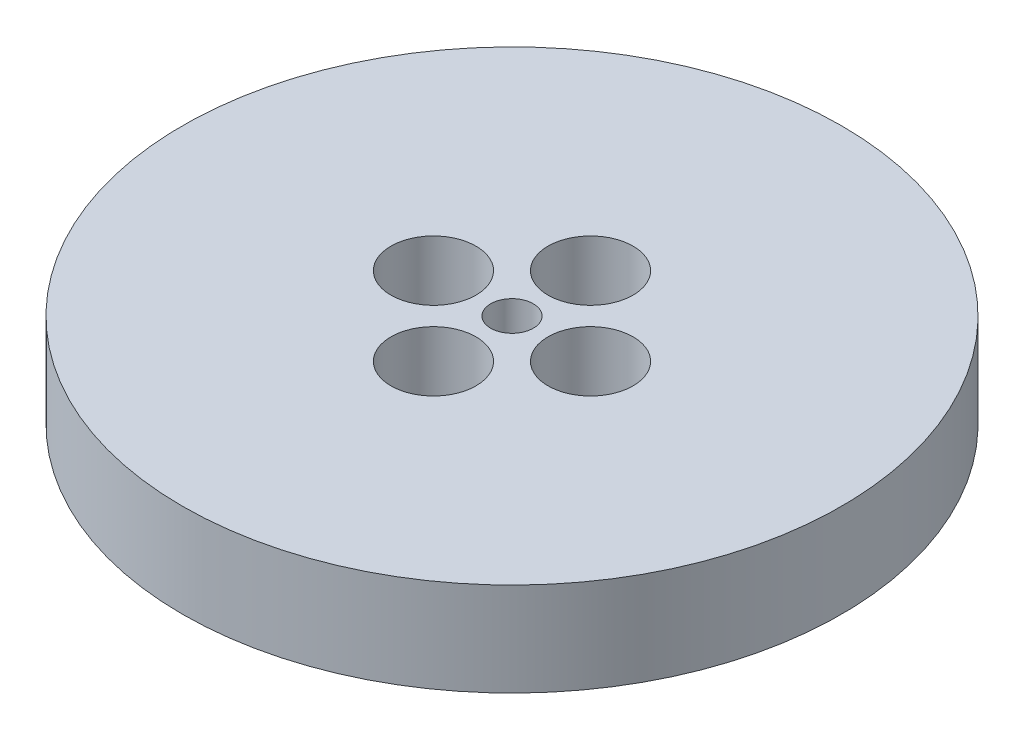
SolidWorks part; units mm, degrees
ref_plane "Front Plane" through (0, 0, 0) normal (0, 0, 1) x (1, 0, 0)
ref_plane "Top Plane" through (0, 0, 0) normal (0, 1, 0) x (1, 0, 0)
ref_plane "Right Plane" through (0, 0, 0) normal (1, 0, 0) x (0, 0, -1)
sketch "Sketch1" plane through (0, 0, 0) normal (0, 1, 0) x (1, 0, 0)
  circle A0 centre (0, 0) radius 77.5
  dimension "FLANGE_OD" = 155
extrude "Boss-Extrude1" add sketch "Sketch1" along normal blind 22
sketch "Sketch2" plane through (0, 0, 0) normal (0, 1, 0) x (1, 0, 0)
  circle A0 centre (0, 0) radius 5
  dimension "BORE_D" = 10
extrude "Cut-Extrude1" cut sketch "Sketch2" along normal through all
sketch "Sketch3" plane through (0, 22, 0) normal (0, 1, 0) x (1, 0, 0)
  circle A0 centre (0, 0) radius 18.4702 construction
  circle A1 centre (-18.4702, 0) radius 10
  dimension "BOLT_D" = 20
  dimension "BOLT_PCD" = 36.9403
extrude "Cut-Extrude2" cut sketch "Sketch3" against normal blind 16.5711
pattern_circular "CirPattern1" count 4 over 360 about axis through (0, 0, 0) along (0, 1, 0) of "Cut-Extrude2"
